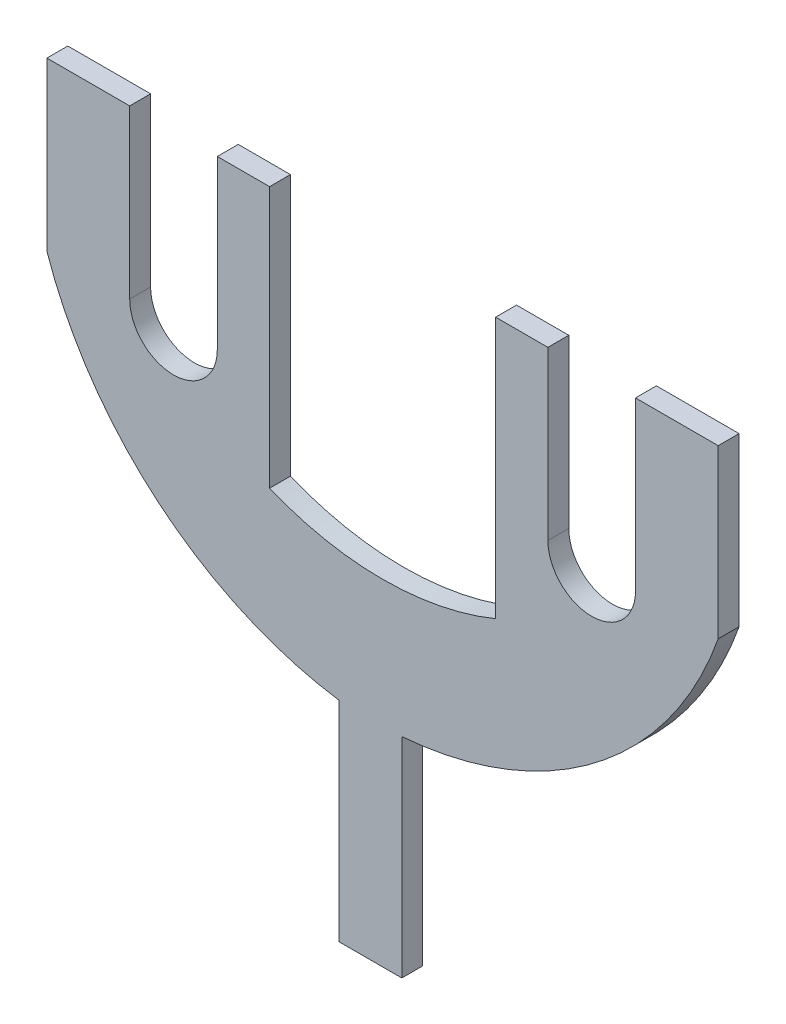
SolidWorks part; units mm, degrees
material "6061-T4 (SS)"
ref_plane "Front Plane" through (0, 0, 0) normal (0, 0, 1) x (1, 0, 0)
ref_plane "Top Plane" through (0, 0, 0) normal (0, 1, 0) x (1, 0, 0)
ref_plane "Right Plane" through (0, 0, 0) normal (1, 0, 0) x (0, 0, -1)
sketch "Sketch2" plane through (0, 0, 0) normal (0, 0, 1) x (1, 0, 0)
  line L0 (-21.105, 21.4878) -> (-17.145, 21.4878)
  line L1 (-21.105, 21.4878) -> (-21.105, 13.4878)
  line L2 (-10.455, 21.4878) -> (-10.455, 8.9983)
  line L4 (-21.105, 13.4878) -> (11, 13.4878) construction
  line L5 (11, 21.4878) -> (11, 8.9983) construction
  line L6 (-5.6315, 15.6192) -> (-5.6315, -8.1259) construction
  line L9 (-17.145, 13.4878) -> (-17.145, 21.4878)
  line L10 (11, 21.4878) -> (-25, 21.4878) construction
  line L13 (-12.955, 13.4878) -> (-12.955, 21.4878)
  line L14 (-12.955, 21.4878) -> (-10.455, 21.4878)
  line L16 (7.045, 13.4878) -> (7.045, 21.4878)
  line L17 (11, 13.4878) -> (11, 21.4878)
  line L22 (2.855, 13.4878) -> (2.855, 21.4878)
  line L23 (2.855, 21.4878) -> (0.355, 21.4878)
  line L24 (0.355, 21.4878) -> (0.355, 8.9983)
  line L25 (7.045, 21.4878) -> (11, 21.4878)
  line L28 (-7.1315, 1.8741) -> (-7.1315, -8.1259)
  line L29 (-7.1315, -8.1259) -> (-4.1315, -8.1259)
  line L30 (-4.1315, -8.1259) -> (-4.1315, 1.8741)
  arc A0 (-21.105, 13.4878) -> (-7.1315, 1.8741) centre (-4.558, 19.1838) ccw
  arc A1 (0.355, 8.9983) -> (-10.455, 8.9983) centre (-5.05, 22.1244) cw
  arc A2 (-17.145, 13.4878) -> (-12.955, 13.4878) centre (-15.05, 13.4878) ccw
  arc A3 (2.855, 13.4878) -> (7.045, 13.4878) centre (4.95, 13.4878) ccw
  arc A5 (11, 13.4878) -> (-4.1315, 1.8741) centre (-5.4993, 19.3206) cw
  dimension "D1" = 2.5
  dimension "D9" = 17.5
  dimension "D10" = 17.5
  dimension "D2" = 2.5
  dimension "D3" = 10
  dimension "D4" = 4.19
  dimension "D5" = 4.19
  dimension "D6" = 3
  dimension "D7" = 3.955
  dimension "D8" = 3.96
extrude "Boss-Extrude2" add sketch "Sketch2" along normal blind 1
